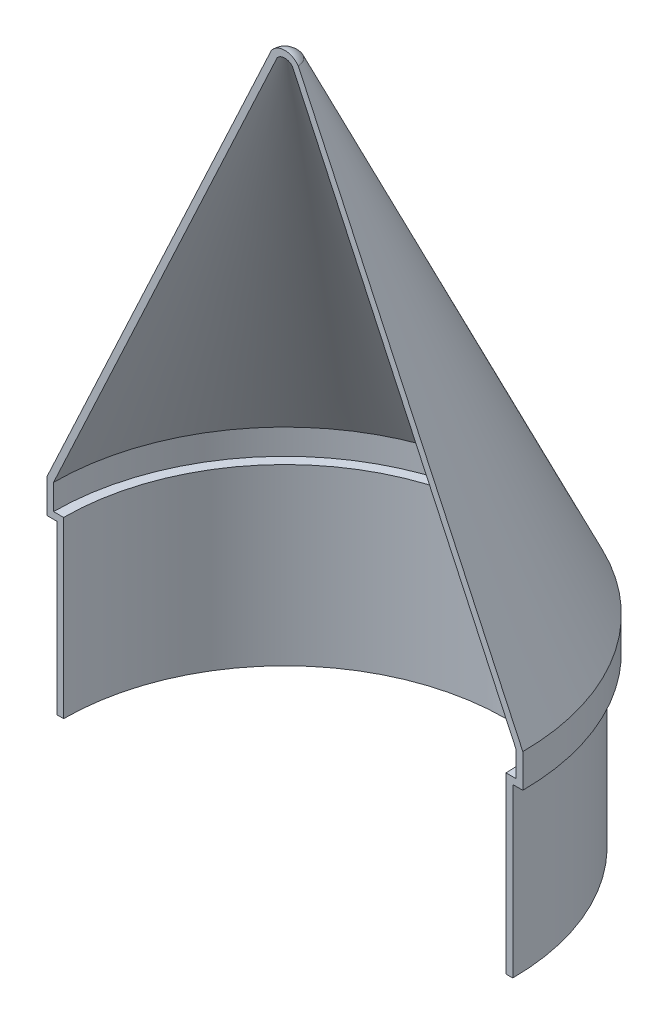
SolidWorks part; units mm, degrees
ref_plane "Front Plane" through (0, 0, 0) normal (0, 0, 1) x (1, 0, 0)
ref_plane "Top Plane" through (0, 0, 0) normal (0, 1, 0) x (1, 0, 0)
ref_plane "Right Plane" through (0, 0, 0) normal (1, 0, 0) x (0, 0, -1)
sketch "Sketch3" plane through (0, 0, 0) normal (0, 0, 1) x (1, 0, 0)
  line L1 (0, 0) -> (0, 155.682)
  line L4 (0, 0) -> (0, -50)
  line L5 (0, -50) -> (68, -50)
  line L6 (68, -50) -> (68, 0)
  line L9 (71, 0) -> (71, 10)
  line L11 (68, 0) -> (71, 0)
  line L12 (4, 153.682) -> (71, 10)
  line L13 (0, 229.1763) -> (0, 65.794) construction
  arc A0 (0, 155.682) -> (4, 153.682) centre (0, 150.682) cw
  point P11 (68, -50)
  point P14 (71, 10)
  dimension "Round yDim" = 2
  dimension "Lip Height" = 10
  dimension "Shoulder Height" = 50
  dimension "Half Angle" = 25
  dimension "Shoulder Diam" = 136
  dimension "Outer Diam" = 142
  dimension "Round xDim" = 8
revolve "Revolve1" add sketch "Sketch3" angle 360 about L1
shell "Shell1" thickness 2 removed face at (0, -50, -68)
sketch "Sketch4" plane through (0, 0, 0) normal (0, 0, 1) x (1, 0, 0)
  line L0 (68, -50) -> (-68, -50)
  line L1 (68, -50) -> (-68, -50)
  line L2 (-68, -50) -> (-68, 0)
  line L3 (-68, -50) -> (-68, 0)
  line L4 (-68, 0) -> (-71, 0)
  line L5 (-68, 0) -> (-71, 0)
  line L6 (-71, 0) -> (-71, 10)
  line L7 (-71, 0) -> (-71, 10)
  line L8 (-71, 10) -> (-4, 153.682)
  line L9 (-71, 10) -> (-4, 153.682)
  line L10 (4, 153.682) -> (71, 10)
  line L11 (4, 153.682) -> (71, 10)
  line L12 (71, 10) -> (71, 0)
  line L13 (71, 10) -> (71, 0)
  line L14 (71, 0) -> (68, 0)
  line L15 (71, 0) -> (68, 0)
  line L16 (68, 0) -> (68, -50)
  line L17 (68, 0) -> (68, -50)
  arc A0 (4, 153.682) -> (-4, 153.682) centre (0, 150.682) ccw
  arc A1 (4, 153.682) -> (-4, 153.682) centre (0, 150.682) ccw
extrude "Cut-Extrude1" cut sketch "Sketch4" along normal through all
